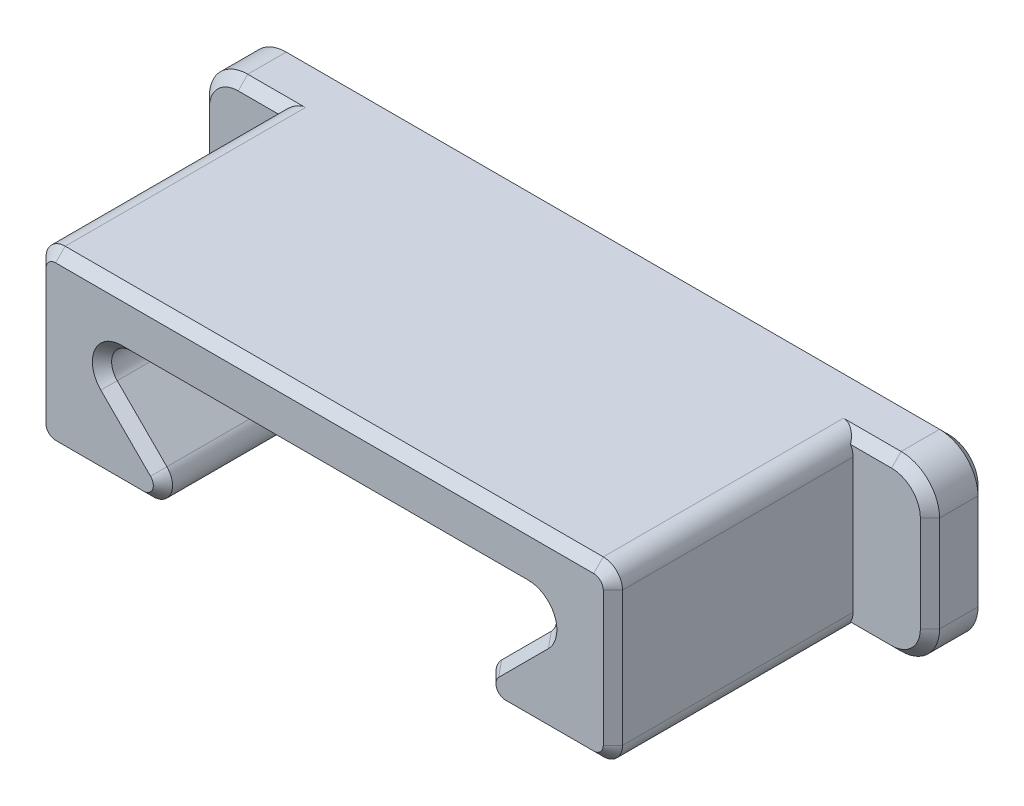
SolidWorks part; units mm, degrees
material "6061 合金"
ref_plane "前视基准面" through (0, 0, 0) normal (0, 0, 1) x (1, 0, 0)
ref_plane "上视基准面" through (0, 0, 0) normal (0, 1, 0) x (1, 0, 0)
ref_plane "右视基准面" through (0, 0, 0) normal (1, 0, 0) x (0, 0, -1)
other "Configuration Table"
sketch "草图1" plane through (0, 0, 0) normal (0, 0, 1) x (1, 0, 0)
  line L0 (-10.0832, 0) -> (8.1555, 0) construction
  line L1 (0, 5.8571) -> (0, -7.8589) construction
  line L3 (-17, -4.5) -> (17, -4.5)
  line L4 (-19, -2.5) -> (-19, 2.5)
  line L5 (-17, 4.5) -> (17, 4.5)
  line L6 (19, -2.5) -> (19, 2.5)
  line L7 (-19, -4.5) -> (19, 4.5) construction
  line L8 (-19, 4.5) -> (19, -4.5) construction
  arc A0 (-19, 2.5) -> (-17, 4.5) centre (-17, 2.5) cw
  arc A1 (-17, -4.5) -> (-19, -2.5) centre (-17, -2.5) cw
  arc A2 (17, -4.5) -> (19, -2.5) centre (17, -2.5) ccw
  arc A3 (17, 4.5) -> (19, 2.5) centre (17, 2.5) cw
  point P4 (0, 0)
  dimension "D3" = 2
  dimension "D1" = 38
  dimension "D2" = 9
extrude "凸台-拉伸1" add sketch "草图1" along normal blind 3
sketch "草图2" plane through (0, 0, 3) normal (0, 0, 1) x (1, 0, 0)
  line L0 (0, 52.105) -> (0, -40.6941) construction
  line L1 (-15, 3.5) -> (-15, -3.5)
  line L2 (-14, -4.5) -> (-9.4142, -4.5)
  line L3 (-8.7071, -2.7929) -> (-11.2929, -0.2071)
  line L4 (-10.5858, 1.5) -> (10.5858, 1.5)
  line L5 (-14, 4.5) -> (14, 4.5)
  line L6 (8.7071, -2.7929) -> (11.2929, -0.2071)
  line L7 (14, -4.5) -> (9.4142, -4.5)
  line L8 (15, 3.5) -> (15, -3.5)
  line L9 (17, 4.5) -> (-17, 4.5) construction
  line L10 (-17, -4.5) -> (17, -4.5) construction
  arc A0 (8.7071, -2.7929) -> (9.4142, -4.5) centre (9.4142, -3.5) ccw
  arc A1 (-9.4142, -4.5) -> (-8.7071, -2.7929) centre (-9.4142, -3.5) ccw
  arc A2 (-15, -3.5) -> (-14, -4.5) centre (-14, -3.5) ccw
  arc A3 (-15, 3.5) -> (-14, 4.5) centre (-14, 3.5) cw
  arc A4 (15, 3.5) -> (14, 4.5) centre (14, 3.5) ccw
  arc A5 (14, -4.5) -> (15, -3.5) centre (14, -3.5) ccw
  arc A6 (-11.2929, -0.2071) -> (-10.5858, 1.5) centre (-10.5858, 0.5) cw
  arc A7 (11.2929, -0.2071) -> (10.5858, 1.5) centre (10.5858, 0.5) ccw
  point P8 (0, 4.5)
  point P9 (0, 1.5)
  point P28 (7.3503, 32.5342)
  point P36 (7, -4.5)
  dimension "D1" = 1
  dimension "D4" = 1
  dimension "D2" = 45
  dimension "D3" = 3
  dimension "D5" = 30
  dimension "D6" = 14
extrude "凸台-拉伸2" add sketch "草图2" along normal blind 12.5
sketch "草图7" plane through (0, 0, 3) normal (0, 0, 1) x (1, 0, 0)
  line L0 (-10.5858, 1.5) -> (10.5858, 1.5) construction
  line L1 (-3.5, 1.5) -> (3.5, 1.5)
  line L2 (-3.5, 1.5) -> (-3.5, -4.5)
  line L3 (-3.5, -4.5) -> (3.5, -4.5)
  line L4 (3.5, 1.5) -> (3.5, -4.5)
  line L5 (-9.4142, -4.5) -> (9.4142, -4.5) construction
  line L6 (0, 6.431) -> (0, -9.2607) construction
  dimension "D1" = 7
extrude "凸台-拉伸3" add sketch "草图7" along normal blind 3
fillet "圆角1" radius 1 4 edges at (-3.5, 1.5, 4.5) (-3.5, -4.5, 4.5) (3.5, -4.5, 4.5) (3.5, 1.5, 4.5)
hole_wizard "M3 螺纹孔1" positions "草图5" profile "草图6" tap size "M3" standard "GB" end condition up to next
sketch "草图5" plane through (0, 0, 6) normal (0, 0, 1) x (1, 0, 0)
  line L0 (-9.4142, -4.5) -> (-2.5, -4.5) construction
  point P0 (0, -1.5)
  dimension "D1" = 3
sketch "草图6" plane through (0, -1.5, 6) normal (1, 0, 0) x (0, -1, 0)
  line L0 (0, 0) -> (0, 6)
  line L1 (0, 6) -> (1.25, 6)
  line L2 (1.25, 6) -> (1.25, 0)
  line L5 (1.25, 0) -> (0, 0)
  line L11 (0, -6.35) -> (0, 107.95) construction
  dimension "通孔螺纹孔钻头直径" = 2.5
  dimension "通孔螺纹孔钻头深度" = 6
cosmetic thread "孔螺蚊线3" parameters "D2"=3
chamfer "倒角1" distance 0.5 angle 45 43 edges at (15.5, -4.5, 3) (18.4142, -3.9142, 3) (19, 0, 3) (18.4142, 3.9142, 3) (15.5, 4.5, 3) (0, 1.5, 15.5) (11.5097, 0.8827, 15.5) (-11.5097, 0.8827, 15.5) (10, -1.5, 15.5) (-10, -1.5, 15.5) (8.4903, -3.8827, 15.5) (-8.4903, -3.8827, 15.5) (11.7071, -4.5, 15.5) (-11.7071, -4.5, 15.5) (14.7071, -4.2071, 15.5) (-14.7071, -4.2071, 15.5) (15, 0, 15.5) (-15, 0, 15.5) (14.7071, 4.2071, 15.5) (-14.7071, 4.2071, 15.5) (0, 4.5, 15.5) (-15.5, -4.5, 3) (-18.4142, -3.9142, 3) (-19, 0, 3) (-18.4142, 3.9142, 3) (-15.5, 4.5, 3) (0, -4.5, 0) (18.4142, -3.9142, 0) (-18.4142, -3.9142, 0) (19, 0, 0) (-19, 0, 0) (18.4142, 3.9142, 0) (-18.4142, 3.9142, 0) (0, 4.5, 0) (-5.9571, -4.5, 3) (5.9571, -4.5, 3) (-3.7929, 1.2071, 6) (-3.5, -1.5, 6) (-3.2071, -4.2071, 6) (3.7929, 1.2071, 6) (0, -4.5, 6) (3.5, -1.5, 6) (3.2071, -4.2071, 6)
